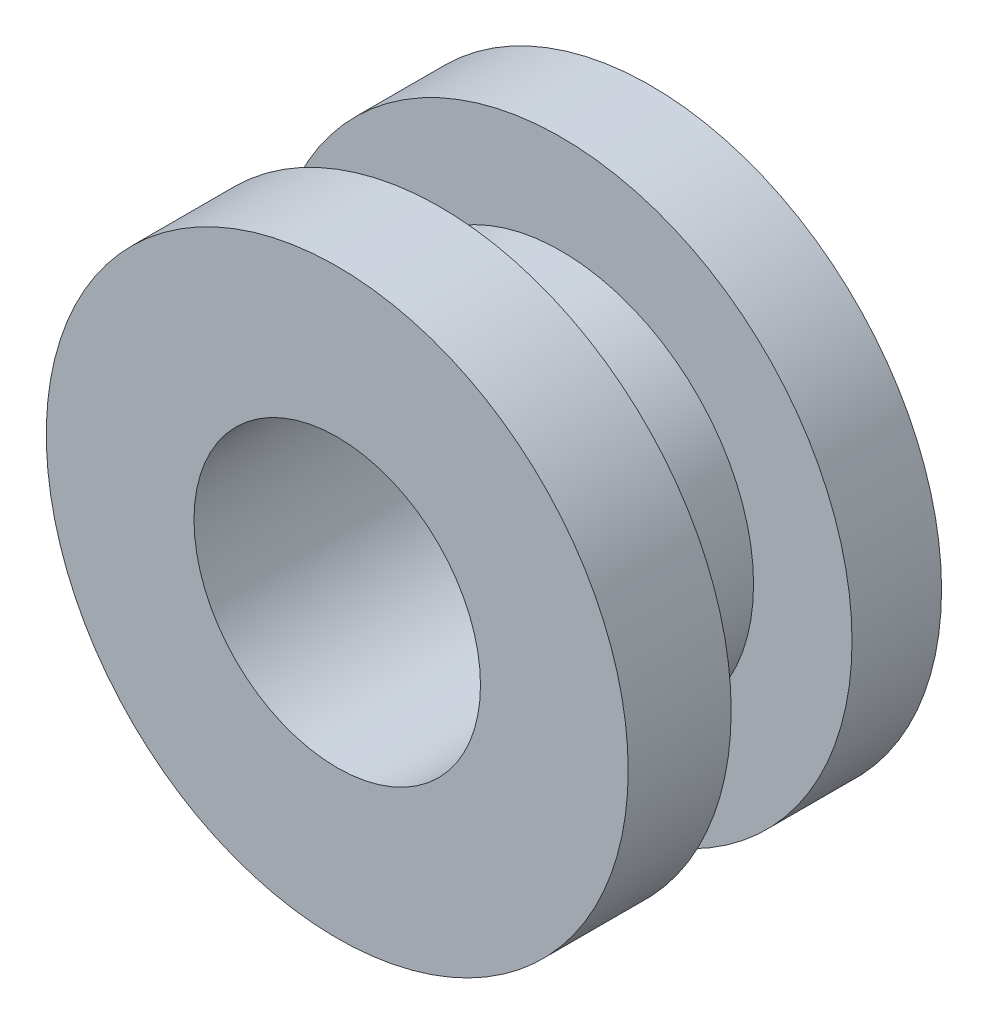
SolidWorks part; units mm, degrees
ref_plane "Plano frontal" through (0, 0, 0) normal (0, 0, 1) x (1, 0, 0)
ref_plane "Plano superior" through (0, 0, 0) normal (0, 1, 0) x (1, 0, 0)
ref_plane "Plano direito" through (0, 0, 0) normal (1, 0, 0) x (0, 0, -1)
sketch "Esboço1" plane through (0, 0, 0) normal (1, 0, 0) x (0, 0, -1)
  line L0 (0, 0) -> (0, 6.5)
  line L1 (-7, 6.5) -> (-4.7, 6.5)
  line L2 (-7, 6.5) -> (-7, 0)
  line L3 (-7, 0) -> (0, 0)
  line L4 (0, 0) -> (-0.444, 0)
  line L5 (-4.7, 6.5) -> (-4.7, 4.3)
  line L6 (-4.7, 4.3) -> (-2, 4.3)
  line L7 (-2, 4.3) -> (-2, 6.5)
  line L8 (-2, 6.5) -> (0, 6.5)
  dimension "D1" = 6.5
  dimension "D2" = 2.7
  dimension "D3" = 4.3
  dimension "D4" = 2
  dimension "D5" = 2.3
revolve "Revolução1" add sketch "Esboço1" angle 360 about L3 region at (0, 2.9272, 3.5225)
hole_wizard "Furo com folga de M61" positions "Esboço3" profile "Esboço2" hole size "M6" standard "ISO" end condition through all
sketch "Esboço3" plane through (0, 0, 0) normal (0, 0, -1) x (-1, 0, 0)
  point P0 (0, 0)
sketch "Esboço2" plane through (0, 0, 0) normal (1, 0, 0) x (0, 1, 0)
  line L0 (0, 0) -> (0, 7)
  line L1 (0, 7) -> (3.2, 7)
  line L2 (3.2, 7) -> (3.2, 0)
  line L5 (3.2, 0) -> (0, 0)
  line L11 (0, -6.35) -> (0, 107.95) construction
  dimension "Thru Hole Dia." = 6.4
  dimension "Thru Hole Depth" = 7
ref_axis "Eixo1" through (0, 0, 7) along (0, 0, -1)
